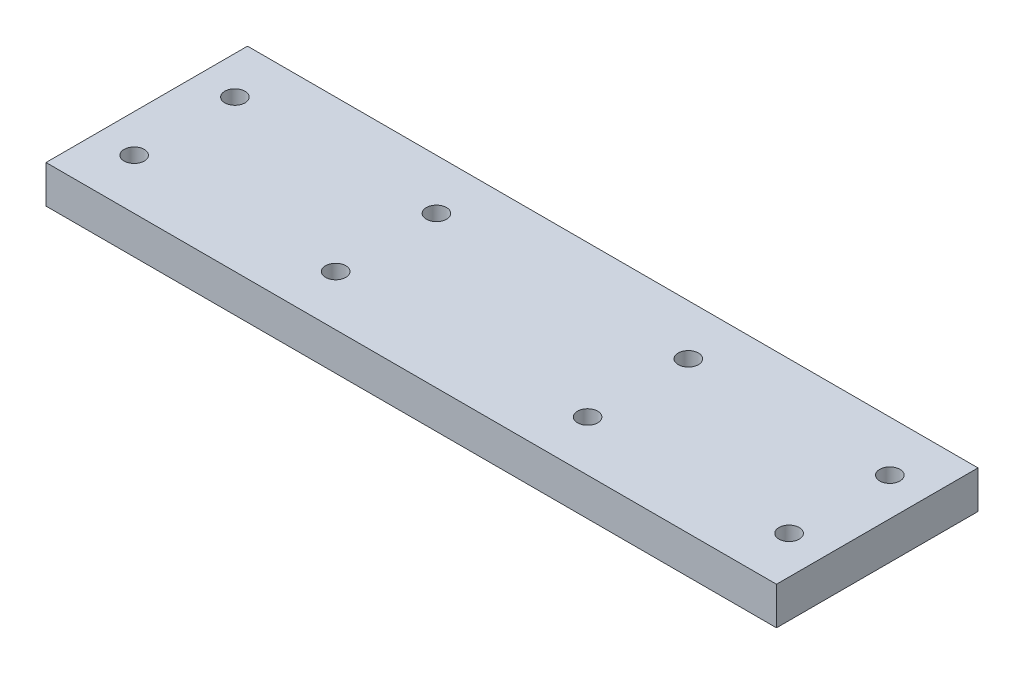
SolidWorks part; units mm, degrees
ref_plane "Front Plane" through (0, 0, 0) normal (0, 0, 1) x (1, 0, 0)
ref_plane "Top Plane" through (0, 0, 0) normal (0, 1, 0) x (1, 0, 0)
ref_plane "Right Plane" through (0, 0, 0) normal (1, 0, 0) x (0, 0, -1)
sketch "Sketch1" plane through (0, 0, 0) normal (0, 1, 0) x (1, 0, 0)
  line L1 (0, 0) -> (184.15, 0)
  line L2 (0, 0) -> (0, 50.8)
  line L3 (0, 50.8) -> (184.15, 50.8)
  line L4 (184.15, 0) -> (184.15, 50.8)
  dimension "D1" = 184.15
  dimension "D2" = 50.8
extrude "Boss-Extrude1" add sketch "Sketch1" along normal blind 9.525
hole_wizard "#10 Clearance Hole1" positions "Sketch2" profile "Sketch3" hole size "#10" standard "ANSI Inch" end condition up to next
sketch "Sketch2" plane through (0, 9.525, 0) normal (0, 1, 0) x (1, 0, 0)
  line L0 (0, 50.8) -> (0, 0) construction
  line L1 (184.15, 50.8) -> (0, 50.8) construction
  line L2 (0, 0) -> (184.15, 0) construction
  line L3 (184.15, 0) -> (184.15, 50.8) construction
  point P0 (9.525, 38.1)
  point P2 (9.525, 12.7)
  point P4 (60.325, 12.7)
  point P6 (60.325, 38.1)
  point P8 (123.825, 38.1)
  point P10 (123.825, 12.7)
  point P12 (174.625, 12.7)
  point P14 (174.625, 38.1)
  dimension "D1" = 9.525
  dimension "D2" = 12.7
  dimension "D3" = 9.525
  dimension "D4" = 12.7
  dimension "D5" = 12.7
  dimension "D6" = 50.8
  dimension "D7" = 12.7
  dimension "D8" = 50.8
  dimension "D9" = 12.7
  dimension "D10" = 9.525
  dimension "D11" = 12.7
  dimension "D12" = 9.525
  dimension "D13" = 50.8
  dimension "D14" = 12.7
  dimension "D15" = 12.7
  dimension "D16" = 50.8
sketch "Sketch3" plane through (9.525, 9.525, -38.1) normal (1, 0, 0) x (0, 0, 1)
  line L0 (0, 0) -> (0, 9.525)
  line L1 (0, 9.525) -> (2.5527, 9.525)
  line L2 (2.5527, 9.525) -> (2.5527, 0)
  line L5 (2.5527, 0) -> (0, 0)
  line L11 (0, -6.35) -> (0, 107.95) construction
  dimension "Thru Hole Dia." = 5.1054
  dimension "Thru Hole Depth" = 9.525
